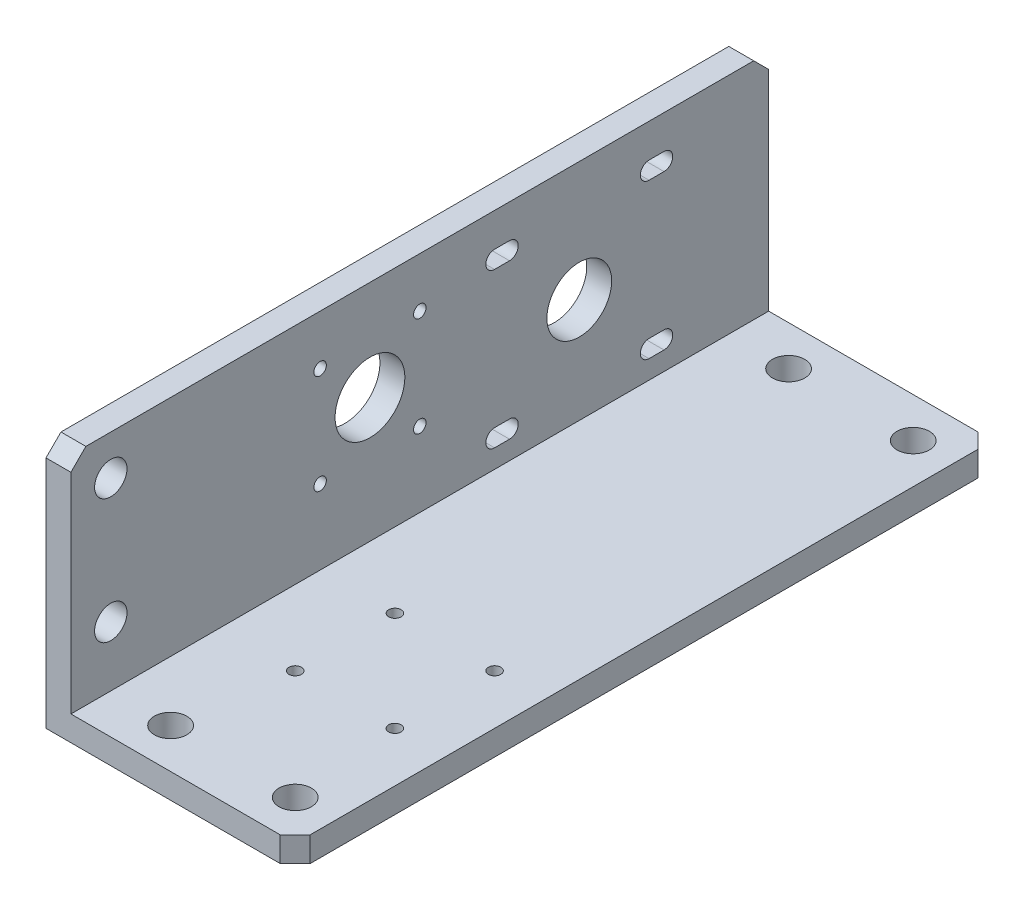
SolidWorks part; units mm, degrees
material "Lega 1060"
ref_plane "Piano frontale" through (0, 0, 0) normal (0, 0, 1) x (1, 0, 0)
ref_plane "Piano superiore" through (0, 0, 0) normal (0, 1, 0) x (1, 0, 0)
ref_plane "Piano destro" through (0, 0, 0) normal (1, 0, 0) x (0, 0, -1)
sketch "Schizzo1" plane through (0, 0, 0) normal (0, 0, 1) x (1, 0, 0)
  line L0 (0, 0) -> (0, 50)
  line L1 (0, 50) -> (5, 50)
  line L2 (5, 50) -> (5, 5)
  line L3 (5, 5) -> (50, 5)
  line L4 (50, 5) -> (50, 0)
  line L5 (50, 0) -> (0, 0)
  dimension "D1" = 5
  dimension "D2" = 5
  dimension "D3" = 50
  dimension "D4" = 50
extrude "Estrusione-Estrusione1" add sketch "Schizzo1" along normal blind 140
sketch "Schizzo2" plane through (0, 0, 0) normal (0, -1, 0) x (1, 0, 0)
  line L0 (5.4524, 132) -> (42.7933, 132) construction
  line L1 (0, 140) -> (50, 140) construction
  line L5 (50, 140) -> (50, 0) construction
  point P4 (17, 132)
  point P5 (42, 132)
  dimension "D1" = 8
  dimension "D2" = 25
  dimension "D3" = 8
sketch "Schizzo3" plane through (0, 0, 0) normal (-1, 0, 0) x (0, 0, 1)
  line L0 (132, 44.621) -> (132, 5.772) construction
  line L1 (140, 50) -> (140, 0) construction
  line L2 (140, 50) -> (0, 50) construction
  point P4 (132, 42)
  point P5 (132, 17)
  dimension "D1" = 8
  dimension "D2" = 8
  dimension "D3" = 25
hole_wizard "Foro Ø6.5 (6.5)-1" positions "Schizzo5" profile "Schizzo4" hole size "Ø6.5" standard "ISO" end condition through all
sketch "Schizzo5" plane through (0, 0, 0) normal (0, -1, 0) x (-1, 0, 0)
  point P0 (-17, -132)
  point P3 (-42, -132)
sketch "Schizzo4" plane through (17, 0, 132) normal (1, 0, 0) x (0, 0, -1)
  line L0 (0, 0) -> (0, 50)
  line L1 (0, 50) -> (3.25, 50)
  line L2 (3.25, 50) -> (3.25, 0)
  line L5 (3.25, 0) -> (0, 0)
  line L11 (0, -6.35) -> (0, 107.95) construction
  dimension "Thru Hole Dia." = 6.5
  dimension "Thru Hole Depth" = 50
hole_wizard "Foro Ø6.5 (6.5)-2" positions "Schizzo7" profile "Schizzo6" hole size "Ø6.5" standard "ISO"
sketch "Schizzo7" plane through (0, 0, 0) normal (-1, 0, 0) x (0, 0, 1)
  point P1 (132, 42)
  point P4 (132, 17)
sketch "Schizzo6" plane through (0, 42, 132) normal (0, 1, 0) x (0, 0, 1)
  line L0 (0, 0) -> (0, 6.9528)
  line L1 (0, 6.9528) -> (3.25, 5)
  line L2 (3.25, 5) -> (3.25, 0)
  line L5 (3.25, 0) -> (0, 0)
  line L10 (0, 6.9528) -> (-3.25, 5) construction
  line L11 (0, -6.35) -> (0, 107.95) construction
  dimension "Hole Dia." = 6.5
  dimension "Hole Depth" = 5
  dimension "Drill Angle" = 118
ref_plane "Piano1" through (0, 0, 70) normal (0, 0, 1) x (1, 0, 0)
mirror "Specchia1" about plane through (0, 0, 70) normal (0, 0, 1) of "Foro Ø6.5 (6.5)-1"
sketch "Schizzo10" plane through (0, 0, 0) normal (-1, 0, 0) x (0, 0, 1)
  line L3 (140, 50) -> (140, 0) construction
  line L5 (140, 50) -> (0, 50) construction
  circle A5 centre (80, 30) radius 7
  point P8 (80, 30)
  point P20 (80, 30)
  dimension "D7" = 14
  dimension "D5" = 60
  dimension "D6" = 20
extrude "Taglio-Estrusione3" cut sketch "Schizzo10" against normal up to next
sketch "Schizzo11" plane through (0, 0, 0) normal (0, -1, 0) x (1, 0, 0)
  line L0 (30, 100) -> (14.4837, 100) construction
  line L1 (30, 100) -> (4.5929, 74.5929) construction
  line L3 (50, 140) -> (50, 0) construction
  line L4 (0, 140) -> (50, 140) construction
  circle A0 centre (20, 90) radius 1.75
  circle A3 centre (20, 110) radius 1.75
  circle A4 centre (40, 110) radius 1.75
  circle A5 centre (40, 90) radius 1.75
  point P2 (30, 100)
  point P17 (30, 100)
  dimension "D2" = 3.5
  dimension "D1" = 20
  dimension "D3" = 45
  dimension "D5" = 20
  dimension "D6" = 40
  dimension "D4" = 4
sketch "Schizzo13" plane through (0, 0, 0) normal (-1, 0, 0) x (0, 0, 1)
  line L0 (71.3802, 26) -> (19.0963, 26) construction
  line L2 (140, 0) -> (0, 0) construction
  line L3 (21, 41.5) -> (24, 41.5) construction
  line L4 (21, 43.25) -> (24, 43.25)
  line L5 (21, 39.75) -> (24, 39.75)
  line L6 (21, 10.5) -> (24, 10.5) construction
  line L7 (21, 8.75) -> (24, 8.75)
  line L8 (21, 12.25) -> (24, 12.25)
  line L9 (38, 26) -> (38, 7.2619) construction
  line L10 (55, 41.5) -> (52, 41.5) construction
  line L11 (55, 43.25) -> (52, 43.25)
  line L12 (55, 39.75) -> (52, 39.75)
  line L13 (55, 10.5) -> (52, 10.5) construction
  line L14 (55, 8.75) -> (52, 8.75)
  line L15 (55, 12.25) -> (52, 12.25)
  arc A0 (55, 43.25) -> (55, 39.75) centre (55, 41.5) cw
  circle A1 centre (80, 30) radius 7 construction
  arc A2 (21, 43.25) -> (21, 39.75) centre (21, 41.5) ccw
  arc A3 (52, 39.75) -> (52, 43.25) centre (52, 41.5) cw
  arc A4 (21, 8.75) -> (21, 12.25) centre (21, 10.5) cw
  arc A5 (24, 12.25) -> (24, 8.75) centre (24, 10.5) cw
  circle A6 centre (38, 26) radius 6.5
  arc A7 (24, 39.75) -> (24, 43.25) centre (24, 41.5) ccw
  arc A10 (55, 8.75) -> (55, 12.25) centre (55, 10.5) ccw
  arc A11 (52, 12.25) -> (52, 8.75) centre (52, 10.5) ccw
  point P8 (38, 26)
  point P13 (53.5, 41.5)
  point P17 (22.5, 10.5)
  point P19 (38, 26)
  point P22 (22.5, 41.5)
  point P40 (53.5, 10.5)
  dimension "D2" = 13
  dimension "D1" = 31
  dimension "D3" = 31
  dimension "D5" = 26
  dimension "D6" = 42
  dimension "D8" = 3.5
  dimension "D9" = 3
extrude "Taglio-Estrusione6" cut sketch "Schizzo13" against normal up to next
chamfer "Smusso1" distance 3 angle 45 4 edges at (50, 2.5, 0) (2.5, 50, 0) (50, 2.5, 140) (2.5, 50, 140)
sketch "Sketch1" plane through (0, 0, 0) normal (-1, 0, 0) x (0, 0, 1)
  line L0 (80, 30) -> (80, 46.7736) construction
  line L1 (80, 46.7736) -> (80, 30) construction
  line L2 (80, 30) -> (63.2264, 46.7736) construction
  line L3 (63.2264, 46.7736) -> (80, 30) construction
  line L4 (80, 30) -> (62.4784, 30) construction
  point P3 (70, 40)
  point P6 (90, 40)
  point P7 (70, 20)
  point P8 (90, 20)
  dimension "D1" = 45
  dimension "D2" = 10
hole_wizard "M3 Tapped Hole1" positions "3DSketch1" profile "Sketch2" tap size "M3" standard "ISO" end condition through all
sketch3d "3DSketch1"
  point P0 (0, 40, 70)
  point P3 (0, 40, 90)
  point P6 (0, 20, 90)
  point P9 (0, 20, 70)
sketch "Sketch2" plane through (0, 40, 70) normal (0, 1, 0) x (0, 0, 1)
  line L0 (0, 0) -> (0, 50)
  line L1 (0, 50) -> (1.25, 50)
  line L2 (1.25, 50) -> (1.25, 0)
  line L5 (1.25, 0) -> (0, 0)
  line L11 (0, -6.35) -> (0, 107.95) construction
  dimension "Thru Tap Drill Dia." = 2.5
  dimension "Thru Tap Drill Depth" = 50
cosmetic thread "Cosmetic Thread1" parameters "D2"=3
cosmetic thread "Cosmetic Thread2" parameters "D2"=3
cosmetic thread "Cosmetic Thread3" parameters "D2"=3
cosmetic thread "Cosmetic Thread4" parameters "D2"=3
hole_wizard "M3 Tapped Hole2" positions "3DSketch2" profile "Sketch3" tap size "M3" standard "ISO" end condition through all
sketch3d "3DSketch2"
  point P0 (20, 0, 110)
  point P3 (40, 0, 110)
  point P6 (40, 0, 90)
  point P9 (20, 0, 90)
sketch "Sketch3" plane through (20, 0, 110) normal (1, 0, 0) x (0, 0, -1)
  line L0 (0, 0) -> (0, 50)
  line L1 (0, 50) -> (1.25, 50)
  line L2 (1.25, 50) -> (1.25, 0)
  line L5 (1.25, 0) -> (0, 0)
  line L11 (0, -6.35) -> (0, 107.95) construction
  dimension "Thru Tap Drill Dia." = 2.5
  dimension "Thru Tap Drill Depth" = 50
cosmetic thread "Cosmetic Thread5" parameters "D2"=3
cosmetic thread "Cosmetic Thread6" parameters "D2"=3
cosmetic thread "Cosmetic Thread7" parameters "D2"=3
cosmetic thread "Cosmetic Thread8" parameters "D2"=3
